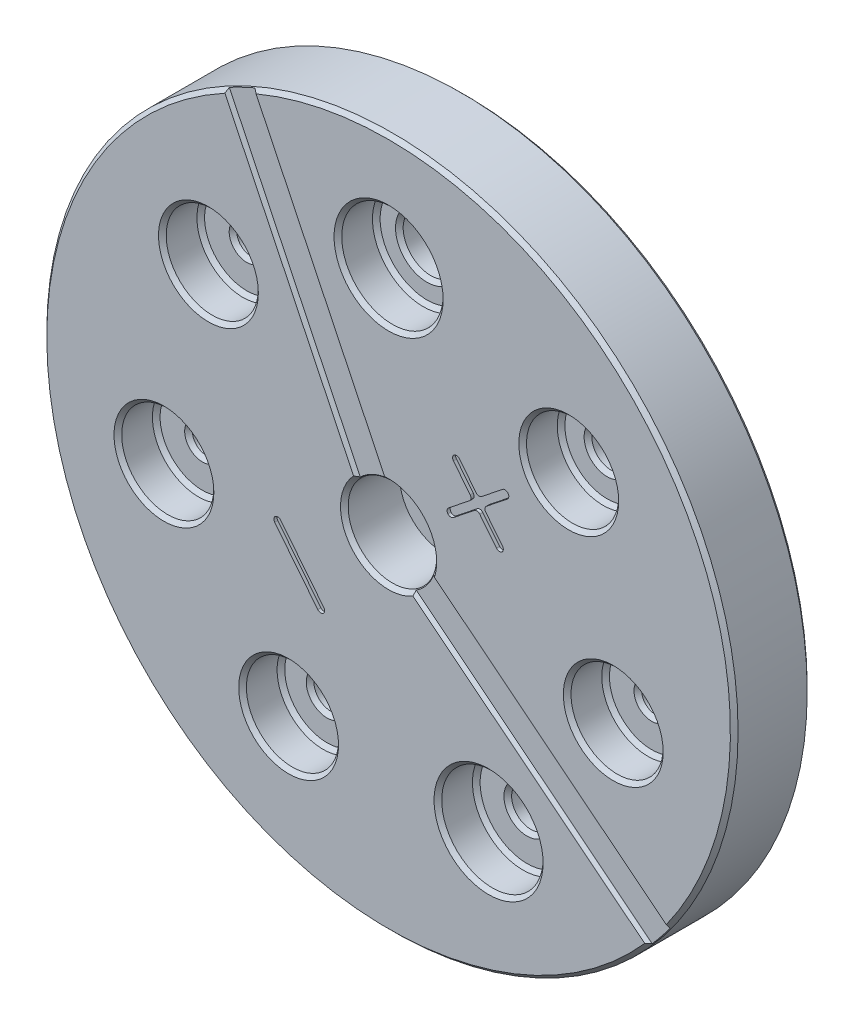
SolidWorks part; units mm, degrees
ref_plane "Front Plane" through (0, 0, 0) normal (0, 0, 1) x (1, 0, 0)
ref_plane "Top Plane" through (0, 0, 0) normal (0, 1, 0) x (1, 0, 0)
ref_plane "Right Plane" through (0, 0, 0) normal (1, 0, 0) x (0, 0, -1)
sketch "Sketch1" plane through (0, 0, 0) normal (0, 0, 1) x (1, 0, 0)
  circle A0 centre (0, 0) radius 28.575
  circle A1 centre (0, 0) radius 19.05 construction
  circle A2 centre (0, 19.05) radius 2.286
  circle A3 centre (14.8939, 11.8775) radius 1.5875
  circle A4 centre (18.5724, -4.239) radius 1.143
  circle A5 centre (8.2655, -17.1635) radius 1.5875
  circle A6 centre (-8.2655, -17.1635) radius 1.397
  circle A7 centre (-18.5724, -4.239) radius 1.143
  circle A8 centre (-14.8939, 11.8775) radius 1.143
  circle A9 centre (0, 19.05) radius 6.731 construction
  circle A10 centre (14.8939, 11.8775) radius 6.731 construction
  circle A11 centre (0, 0) radius 2.159
  point P4 (0, 19.05)
  point P5 (14.8939, 11.8775)
  point P8 (18.5724, -4.239)
  point P9 (8.2655, -17.1635)
  point P10 (-8.2655, -17.1635)
  point P11 (-18.5724, -4.239)
  point P12 (-14.8939, 11.8775)
  point P13 (0, 0)
  dimension "D1" = 57.15
  dimension "D2" = 38.1
  dimension "D4" = 2.286
  dimension "D5" = 3.175
  dimension "D6" = 4.572
  dimension "D7" = 3.175
  dimension "D8" = 2.794
  dimension "D9" = 2.286
  dimension "D10" = 2.286
  dimension "D11" = 13.462
  dimension "D12" = 4.318
  dimension "D3" = 7
extrude "Boss-Extrude1" add sketch "Sketch1" along normal blind 6.35
sketch "Sketch2" plane through (0, 0, 6.35) normal (0, 0, 1) x (1, 0, 0)
  circle A1 centre (0, 19.05) radius 4.191
  circle A2 centre (14.8939, 11.8775) radius 3.81
  circle A3 centre (18.5724, -4.239) radius 3.81
  circle A4 centre (8.2655, -17.1635) radius 4.191
  circle A5 centre (-8.2655, -17.1635) radius 3.81
  circle A6 centre (-18.5724, -4.239) radius 3.81
  circle A7 centre (-14.8939, 11.8775) radius 3.81
  dimension "D1" = 8.382
  dimension "D2" = 7.62
extrude "Cut-Extrude1" cut sketch "Sketch2" against normal blind 3.175
sketch "Sketch3" plane through (0, 0, 6.35) normal (0, 0, 1) x (1, 0, 0)
  circle A0 centre (0, 0) radius 3.6576
  dimension "D1" = 7.3152
extrude "Cut-Extrude2" cut sketch "Sketch3" against normal blind 4.572
chamfer "Chamfer1" distance 0.3175 angle 45 33 edges at (2.159, 0, 0) (-13.7509, 11.8775, 0) (-17.4294, -4.239, 0) (-6.8685, -17.1635, 0) (9.853, -17.1635, 0) (19.7154, -4.239, 0) (2.286, 19.05, 0) (16.4814, 11.8775, 0) (28.575, 0, 0) (-4.4555, -17.1635, 3.175) (-6.8685, -17.1635, 3.175) (12.4565, -17.1635, 3.175) (9.853, -17.1635, 3.175) (22.3824, -4.239, 3.175) (19.7154, -4.239, 3.175) (18.7039, 11.8775, 3.175) (16.4814, 11.8775, 3.175) (4.191, 19.05, 3.175) (2.286, 19.05, 3.175) (-11.0839, 11.8775, 3.175) (-13.7509, 11.8775, 3.175) (-14.7624, -4.239, 3.175) (-17.4294, -4.239, 3.175) (28.575, 0, 6.35) (4.191, 19.05, 6.35) (-11.0839, 11.8775, 6.35) (-14.7624, -4.239, 6.35) (-4.4555, -17.1635, 6.35) (12.4565, -17.1635, 6.35) (22.3824, -4.239, 6.35) (18.7039, 11.8775, 6.35) (3.6576, 0, 6.35) (2.159, 0, 1.778)
sketch "Sketch5" plane through (0, 0, 6.35) normal (0, 0, 1) x (1, 0, 0)
  line L0 (2.8596, 2.2805) -> (11.9151, 9.502) construction
  line L1 (4.9051, 3.9117) -> (9.8697, 7.8708)
  line L2 (9.3669, 3.4089) -> (5.4078, 8.3735)
  line L3 (-9.3669, -3.4089) -> (-5.4078, -8.3735)
  line L4 (0, 0) -> (-18.5389, -14.7843) construction
  circle A1 centre (14.8939, 11.8775) radius 3.81 construction
  circle A2 centre (0, 0) radius 3.6576 construction
  point P8 (7.3874, 5.8912)
  point P9 (7.3874, 5.8912)
  point P10 (-7.3874, -5.8912)
  point P11 (7.3874, 5.8912)
  point P13 (0, 0)
  point P16 (0, 0)
  point P20 (14.8939, 11.8775)
  point P24 (0, 0)
  dimension "D1" = 6.35
  dimension "D2" = 2
extrude "Cut-Extrude-Thin2" cut sketch "Sketch5" against normal blind 0.254 thin thin type mid plane wall 0.635
fillet "Fillet1" radius 0.3175 16 edges at (-5.656, -8.5715, 6.223) (-9.6152, -3.6069, 6.223) (-9.1187, -3.211, 6.223) (-5.1596, -8.1756, 6.223) (10.0676, 7.6226, 6.223) (9.6152, 3.6069, 6.223) (9.1187, 3.211, 6.223) (5.103, 3.6634, 6.223) (4.7071, 4.1599, 6.223) (5.1596, 8.1756, 6.223) (9.6717, 8.119, 6.223) (5.656, 8.5715, 6.223) (7.3371, 5.445, 6.223) (7.8336, 5.841, 6.223) (7.4376, 6.3374, 6.223) (6.9412, 5.9415, 6.223)
sketch "Sketch4" plane through (0, 0, 6.35) normal (0, 0, 1) x (1, 0, 0)
  line L0 (-12.3982, 25.7452) -> (0, 0)
  line L1 (0, 0) -> (22.3408, -17.8162)
  line L2 (0, 0) -> (-14.8939, 11.8775) construction
  line L3 (0, 0) -> (0, 19.05) construction
  line L4 (0, 0) -> (8.2655, -17.1635)
  circle A0 centre (0, 0) radius 28.575 construction
  dimension "D1" = 51.429
  dimension "D2" = 25.714
  dimension "D3" = 25.714
extrude "Cut-Extrude-Thin1" cut sketch "Sketch4" against normal blind 0.254 thin contours L0 | L1 thin type mid plane wall 1.5875
chamfer "Chamfer2" distance 0.635 angle 45 4 edges at (12.0697, -10.6405, 6.35) (13.0595, -9.3993, 6.35) (-6.2577, 14.8236, 6.35) (-7.688, 14.1348, 6.35)
equation "\"D2@Sketch4\"=\"D1@Sketch4\"/2"
equation "\"D3@Sketch4\"=\"D2@Sketch4\""
